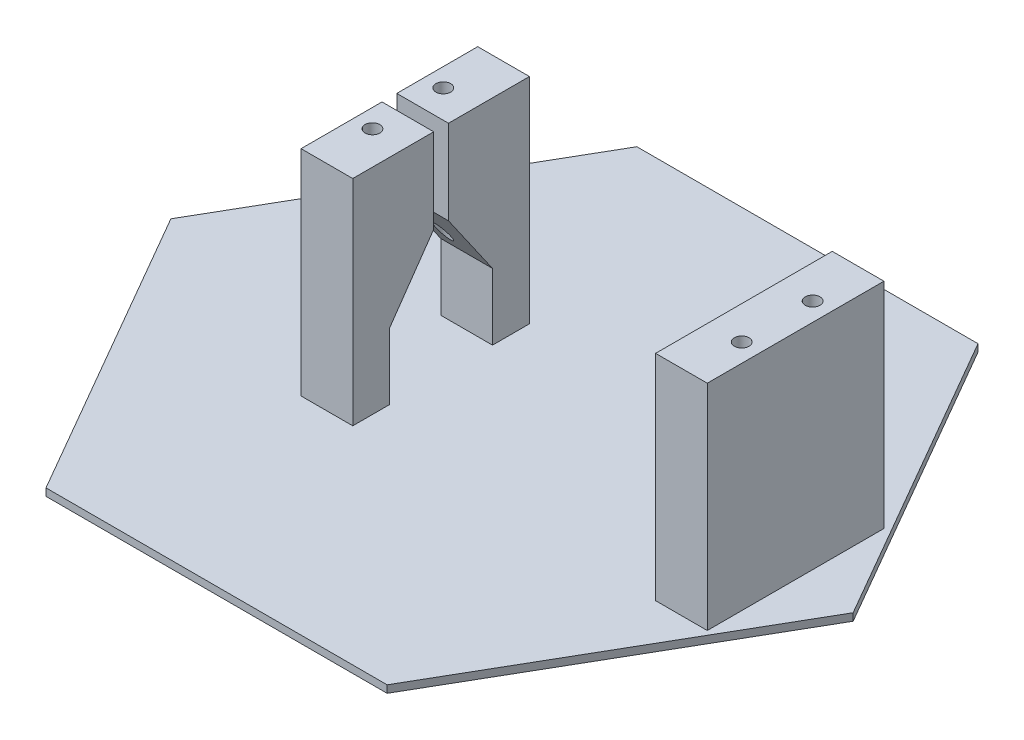
SolidWorks part; units mm, degrees
ref_plane "Front Plane" through (0, 0, 0) normal (0, 0, 1) x (1, 0, 0)
ref_plane "Top Plane" through (0, 0, 0) normal (0, 1, 0) x (1, 0, 0)
ref_plane "Right Plane" through (0, 0, 0) normal (1, 0, 0) x (0, 0, -1)
sketch "Sketch1" plane through (0, 0, 0) normal (0, 1, 0) x (1, 0, 0)
  line L1 (46.188, 0) -> (23.094, 40)
  line L2 (23.094, 40) -> (-23.094, 40)
  line L3 (-23.094, 40) -> (-46.188, 0)
  line L4 (-46.188, 0) -> (-23.094, -40)
  line L5 (-23.094, -40) -> (23.094, -40)
  line L6 (23.094, -40) -> (46.188, 0)
  circle A0 centre (0, 0) radius 40 construction
  dimension "D1" = 80
extrude "Boss-Extrude1" add sketch "Sketch1" along normal blind 1
sketch "Sketch2" plane through (0, 1, 0) normal (0, 1, 0) x (1, 0, 0)
  line L0 (10.9, 11.9602) -> (10.9, -11.9602) construction
  line L5 (-16.6, -11.9602) -> (38.4, -11.9602) construction
  line L6 (-16.6, -11.9602) -> (-16.6, 11.9602) construction
  line L7 (-16.6, 11.9602) -> (38.4, 11.9602) construction
  line L8 (38.4, -11.9602) -> (38.4, 11.9602)
  line L9 (-16.6, 0) -> (38.4, 0) construction
  line L10 (-9.6, 11.9602) -> (-9.6, -11.9602) construction
  line L11 (31.4, 11.9602) -> (31.4, -11.9602)
  line L12 (-16.6, 6.9602) -> (-9.6, 6.9602)
  line L13 (-16.6, -6.9602) -> (-9.6, -6.9602)
  line L14 (31.4, 11.9602) -> (38.4, 11.9602)
  line L15 (31.4, -11.9602) -> (38.4, -11.9602)
  line L16 (-9.6, -11.9602) -> (-16.6, -11.9602)
  line L17 (-16.6, -11.9602) -> (-16.6, -6.9602)
  line L18 (-9.6, -6.9602) -> (-9.6, -11.9602)
  line L19 (-16.6, 6.9602) -> (-16.6, 11.9602)
  line L20 (-16.6, 11.9602) -> (-9.6, 11.9602)
  line L21 (-9.6, 11.9602) -> (-9.6, 6.9602)
  circle A0 centre (-14.1, 4.8) radius 1 construction
  circle A1 centre (-14.1, -4.8) radius 1 construction
  circle A2 centre (35.9, -4.8) radius 1
  circle A3 centre (35.9, 4.8) radius 1
  circle A4 centre (0, 0) radius 4.1718 construction
  circle A5 centre (-14.1, -4.8) radius 1
  circle A6 centre (-14.1, 4.8) radius 1
  point P10 (-9.6, 11.9602)
  point P14 (-9.6, 0)
  point P22 (-16.6, 6.9602)
  dimension "D2" = 4.8
  dimension "D3" = 2.5
  dimension "D5" = 2
  dimension "D1" = 55
  dimension "D4" = 7
  dimension "D6" = 5
  dimension "D7" = 9.6
extrude "Boss-Extrude4" add sketch "Sketch2" along normal blind 29
sketch "Sketch4" plane through (-16.6, 0, 0) normal (-1, 0, 0) x (0, 0, 1)
  line L0 (0, 1) -> (0, 30) construction
  line L1 (-11.9602, 1) -> (11.9602, 1) construction
  line L2 (-11.9602, 30) -> (11.9602, 30) construction
  line L3 (-6.9602, 30) -> (-6.9602, 1) construction
  line L4 (-6.9602, 10) -> (0, 20)
  line L5 (0, 20) -> (0, 30)
  line L6 (6.9602, 30) -> (-6.9602, 30)
  line L7 (-6.9602, 30) -> (-6.9602, 10)
  line L8 (6.9602, 10) -> (0, 20)
  line L9 (6.9602, 30) -> (6.9602, 10)
  point P6 (-6.9602, 10)
  point P7 (0, 20)
  dimension "D1" = 9
  dimension "D2" = 10
extrude "Boss-Extrude5" add sketch "Sketch4" against normal up to surface (7 mm away) contours L8 L9 L6 L7 L4 up to face at (-9.6, 15.5, -9.4602)
extrude "Cut-Extrude1" cut sketch "Sketch2<4>" along normal up to surface (29 mm away) contours A5 | A6 up to face at (-13.1, 30, 0)
sketch "Sketch2<4>" plane through (0, 1, 0) normal (0, 1, 0) x (1, 0, 0) same geometry as "Sketch2"
sketch "Sketch5" plane through (0, 30, 0) normal (0, 1, 0) x (1, 0, 0)
  line L0 (-16.6, 0) -> (-9.6, 0) construction
  line L1 (-16.6, -1) -> (-9.6, -1)
  line L2 (-16.6, 1) -> (-9.6, 1)
  line L3 (-16.6, 1) -> (-16.6, -1)
  line L4 (-9.6, 1) -> (-9.6, -1)
  dimension "D1" = 1
  dimension "D2" = 1
extrude "Cut-Extrude2" cut sketch "Sketch5" against normal up to next contours L4 L1 L3 L2
